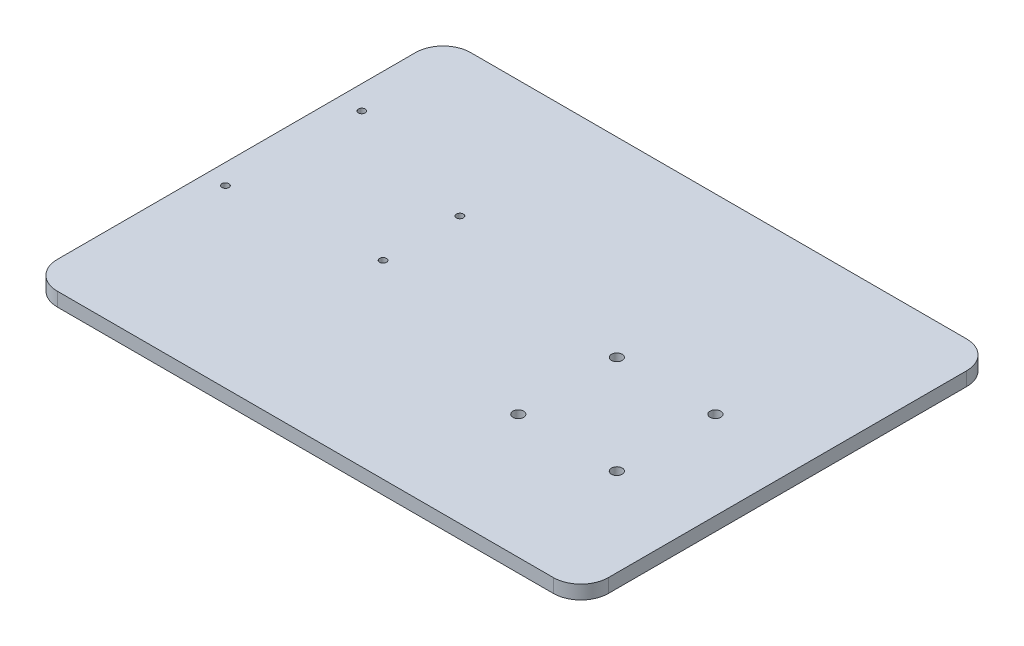
SolidWorks part; units mm, degrees
ref_plane "Front Plane" through (0, 0, 0) normal (0, 0, 1) x (1, 0, 0)
ref_plane "Top Plane" through (0, 0, 0) normal (0, 1, 0) x (1, 0, 0)
ref_plane "Right Plane" through (0, 0, 0) normal (1, 0, 0) x (0, 0, -1)
sketch "Sketch1" plane through (0, 0, 0) normal (0, 1, 0) x (1, 0, 0)
  line L1 (-90, -75) -> (90, -75)
  line L2 (-100, -65) -> (-100, 65)
  line L3 (-90, 75) -> (90, 75)
  line L4 (100, -65) -> (100, 65)
  line L5 (-100, -75) -> (100, 75) construction
  line L6 (-100, 75) -> (100, -75) construction
  arc A0 (90, -75) -> (100, -65) centre (90, -65) ccw
  arc A1 (-90, -75) -> (-100, -65) centre (-90, -65) cw
  arc A2 (-100, 65) -> (-90, 75) centre (-90, 65) cw
  arc A3 (90, 75) -> (100, 65) centre (90, 65) cw
  point P1 (0, 0)
  dimension "D3" = 10
  dimension "D1" = 200
  dimension "D2" = 150
extrude "Boss-Extrude1" add sketch "Sketch1" along normal blind 5 contours L2 A2 L3 A3 L4 A0 L1 A1
hole_wizard "arduino uno holes" positions "Sketch3" profile "Sketch2" hole size "Ø2.5" standard "ANSI Metric" end condition through all
sketch "Sketch3" plane through (0, 5, 0) normal (0, 1, 0) x (1, 0, 0)
  point P0 (-40.587, 21.6843)
  point P2 (-40.587, -6.2157)
  point P4 (-91.387, 36.8843)
  point P6 (-92.687, -11.3157)
  dimension "D1" = 27.9
  dimension "D2" = 15.2
  dimension "D3" = 50.8
  dimension "D4" = 1.3
  dimension "D5" = 5.1
sketch "Sketch2" plane through (-40.587, 5, -21.6843) normal (1, 0, 0) x (0, 0, 1)
  line L0 (0, 0) -> (0, 5)
  line L1 (0, 5) -> (1.25, 5)
  line L2 (1.25, 5) -> (1.25, 0)
  line L5 (1.25, 0) -> (0, 0)
  line L11 (0, -6.35) -> (0, 107.95) construction
  dimension "Thru Hole Dia." = 2.5
  dimension "Thru Hole Depth" = 5
hole_wizard "l298n holes" positions "Sketch9" profile "Sketch8" hole size "#23" standard "ANSI Inch"
sketch "Sketch9" plane through (0, 5, 0) normal (0, 1, 0) x (1, 0, 0)
  point P0 (32.3229, 5.7319)
  point P2 (68.0829, 5.7319)
  point P4 (32.3229, -30.0281)
  point P6 (68.0829, -30.0281)
  dimension "D1" = 35.76
  dimension "D2" = 35.76
sketch "Sketch8" plane through (32.3229, 5, -5.7319) normal (1, 0, 0) x (0, 0, 1)
  line L0 (0, 0) -> (0, 6.1752)
  line L1 (0, 6.1752) -> (1.9558, 5)
  line L2 (1.9558, 5) -> (1.9558, 0)
  line L5 (1.9558, 0) -> (0, 0)
  line L10 (0, 6.1752) -> (-1.9558, 5) construction
  line L11 (0, -6.35) -> (0, 107.95) construction
  dimension "Hole Dia." = 3.9116
  dimension "Hole Depth" = 5
  dimension "Drill Angle" = 118
equation "\"w\"=200"
equation "\"D1@Sketch1\"=\"w\""
equation "\"h\"=150"
equation "\"D2@Sketch1\"=\"h\""
equation "\"th\"=5"
equation "\"D1@Boss-Extrude1\"=\"th\""
